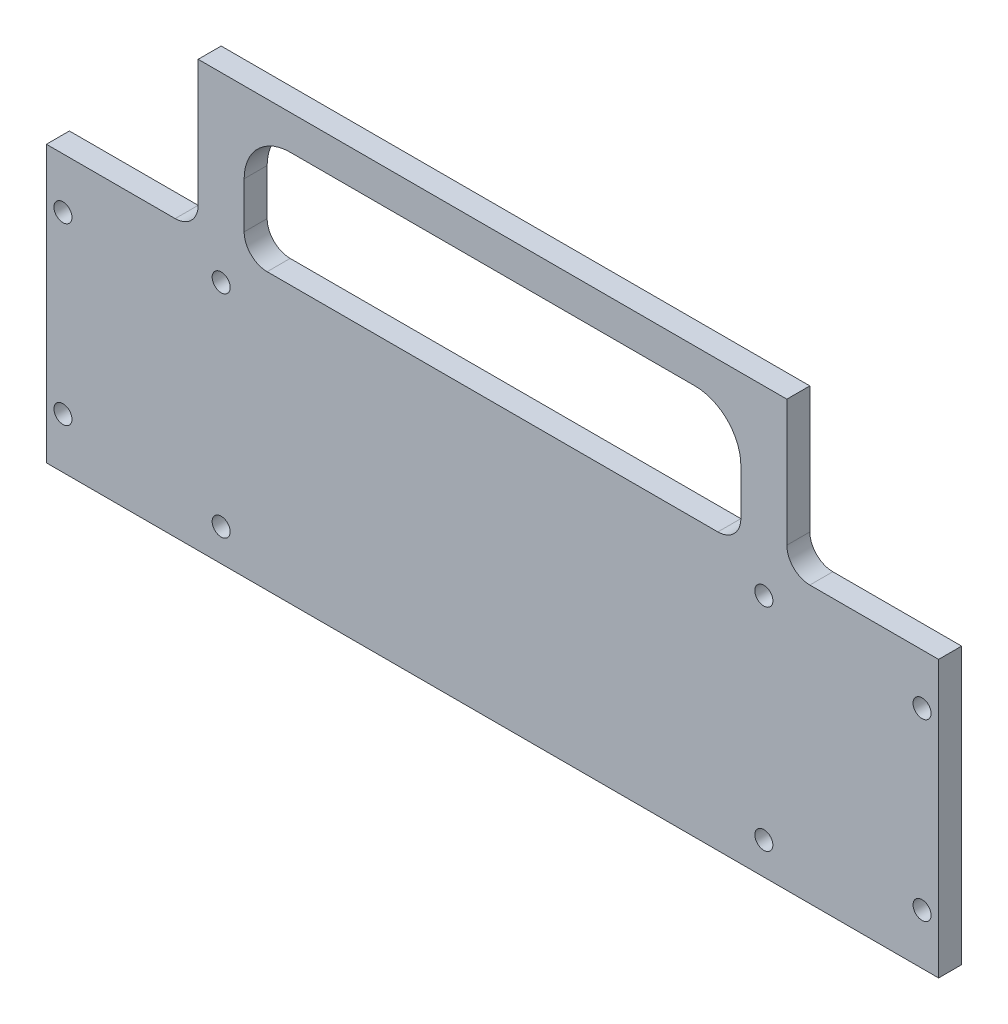
SolidWorks part; units mm, degrees
material "6061-T6 (SS)"
ref_plane "Front Plane" through (0, 0, 0) normal (0, 0, 1) x (1, 0, 0)
ref_plane "Top Plane" through (0, 0, 0) normal (0, 1, 0) x (1, 0, 0)
ref_plane "Right Plane" through (0, 0, 0) normal (1, 0, 0) x (0, 0, -1)
sketch "Sketch1" plane through (0, 0, 0) normal (0, 0, 1) x (1, 0, 0)
  line L1 (-123.19, 38.1) -> (123.19, 38.1)
  line L2 (-123.19, 38.1) -> (-123.19, -38.1)
  line L3 (-123.19, -38.1) -> (123.19, -38.1)
  line L4 (123.19, 38.1) -> (123.19, -38.1)
  line L5 (-123.19, 38.1) -> (123.19, -38.1) construction
  line L6 (-123.19, -38.1) -> (123.19, 38.1) construction
  point P0 (0, 0)
  dimension "D1" = 76.2
  dimension "D2" = 246.38
extrude "Boss-Extrude1" add sketch "Sketch1" along normal blind 6.35
sketch "Sketch2" plane through (0, 0, 6.35) normal (0, 0, 1) x (1, 0, 0)
  line L0 (123.19, -38.1) -> (123.19, 38.1) construction
  line L1 (-74.93, 29.21) -> (74.93, 29.21) construction
  line L2 (-74.93, 29.21) -> (-74.93, -29.21) construction
  line L3 (-74.93, -29.21) -> (74.93, -29.21) construction
  line L4 (74.93, 29.21) -> (74.93, -29.21) construction
  line L5 (-74.93, 29.21) -> (74.93, -29.21) construction
  line L6 (-74.93, -29.21) -> (74.93, 29.21) construction
  line L7 (118.618, -24.13) -> (-118.618, -24.13) construction
  line L8 (118.618, -24.13) -> (118.618, 24.13) construction
  line L9 (118.618, 24.13) -> (-118.618, 24.13) construction
  line L10 (-118.618, -24.13) -> (-118.618, 24.13) construction
  line L11 (118.618, -24.13) -> (-118.618, 24.13) construction
  line L12 (118.618, 24.13) -> (-118.618, -24.13) construction
  point P0 (0, 0)
  point P6 (0, 0)
  dimension "D1" = 149.86
  dimension "D2" = 58.42
  dimension "D3" = 4.572
  dimension "D4" = 48.26
hole_wizard "#10 Clearance Hole1" positions "Sketch3" profile "Sketch4" hole size "#10" standard "ANSI Inch" end condition through all
sketch "Sketch3" plane through (0, 0, 6.35) normal (0, 0, 1) x (1, 0, 0)
  point P0 (-74.93, 29.21)
  point P3 (-74.93, -29.21)
  point P6 (74.93, 29.21)
  point P9 (74.93, -29.21)
  point P12 (-118.618, 24.13)
  point P15 (-118.618, -24.13)
  point P18 (118.618, 24.13)
  point P21 (118.618, -24.13)
sketch "Sketch4" plane through (-74.93, 29.21, 6.35) normal (1, 0, 0) x (0, -1, 0)
  line L0 (0, 0) -> (0, 6.35)
  line L1 (0, 6.35) -> (2.4892, 6.35)
  line L2 (2.4892, 6.35) -> (2.4892, 0)
  line L5 (2.4892, 0) -> (0, 0)
  line L11 (0, -6.35) -> (0, 107.95) construction
  dimension "Thru Hole Dia." = 4.9784
  dimension "Thru Hole Depth" = 6.35
sketch "Sketch5" plane through (0, 0, 6.35) normal (0, 0, 1) x (1, 0, 0)
  line L0 (123.19, 38.1) -> (-123.19, 38.1) construction
  line L1 (-81.28, 38.1) -> (-68.58, 38.1)
  line L2 (-81.28, 38.1) -> (-81.28, 79.375)
  line L3 (-81.28, 79.375) -> (-68.58, 79.375)
  line L4 (-68.58, 38.1) -> (-68.58, 79.375)
  line L6 (-68.58, 79.375) -> (0, 79.375)
  line L7 (-68.58, 79.375) -> (-68.58, 69.85)
  line L8 (-68.58, 69.85) -> (0, 69.85)
  line L9 (0, 79.375) -> (0, 69.85)
  point P9 (-74.93, 38.1)
  point P11 (-74.93, 29.21)
  line M13 (123.19, 38.1) -> (-123.19, 38.1)
  dimension "D1" = 9.525
  dimension "D2" = 12.7
  dimension "D3" = 41.275
extrude "Boss-Extrude2" add sketch "Sketch5" along direction (0, 0, 1) on the side against the normal up to surface (6.35 mm away) contours L4 L3 L2 M13 | L9 L6 L4 L8 region at (-74.93, 58.7375, 6.35) region at (-34.29, 74.6125, 6.35) up to face at (-72.4408, 29.21, 0)
fillet "Fillet1" radius 6.35 2 edges at (-68.58, 38.1, 3.175) (-81.28, 38.1, 3.175)
fillet "Fillet2" radius 12.7 1 edges at (-68.58, 69.85, 3.175)
mirror "Mirror1" about plane through (0, 0, 0) normal (1, 0, 0) of "Fillet2", "Fillet1", "Boss-Extrude2"
